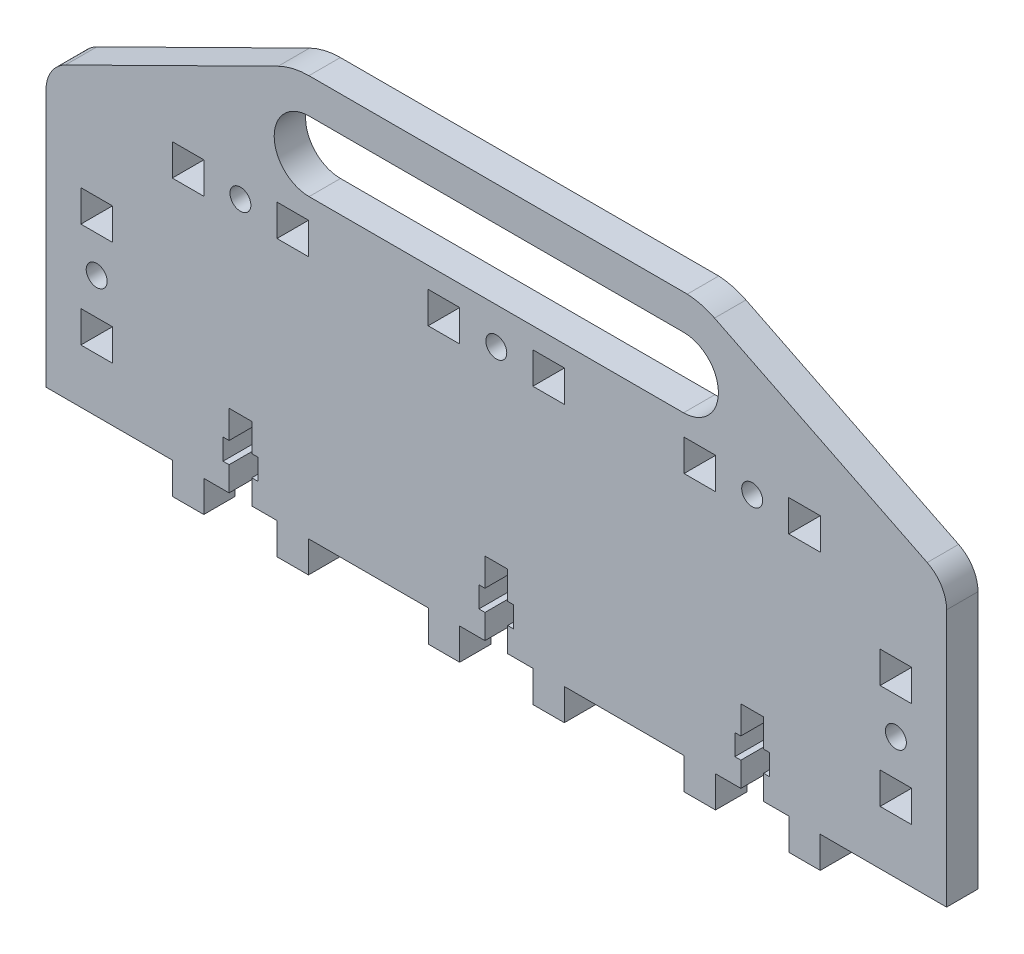
SolidWorks part; units mm, degrees
ref_plane "Front Plane" through (0, 0, 0) normal (0, 0, 1) x (1, 0, 0)
ref_plane "Top Plane" through (0, 0, 0) normal (0, 1, 0) x (1, 0, 0)
ref_plane "Right Plane" through (0, 0, 0) normal (1, 0, 0) x (0, 0, -1)
sketch "Sketch1" plane through (0, 0, 0) normal (0, 0, 1) x (1, 0, 0)
  line L0 (0, 35) -> (0, 0) construction
  line L1 (-110, 0) -> (110, 0)
  line L3 (-110, 70) -> (110, 70) construction
  line L5 (-110, 0) -> (110, 70) construction
  line L6 (-110, 70) -> (110, 0) construction
  line L7 (-53.6553, 95) -> (53.6553, 95) construction
  line L8 (-53.6553, 105) -> (53.6553, 105)
  line L9 (-53.6553, 85) -> (53.6553, 85)
  line L11 (-108.2938, 90.273) -> (-62.5269, 112.9247)
  line L12 (-53.6908, 115) -> (54.7434, 115)
  line L13 (62.5471, 112.9477) -> (117.7112, 85.6176)
  line L15 (0, 35) -> (110, 35) construction
  line L16 (110, 0) -> (129.05, 0)
  line L17 (129.05, 0) -> (129.05, 80)
  line L18 (129.05, 80) -> (117.7112, 85.6176)
  line L19 (-110, 0) -> (-129.05, 0)
  line L20 (-129.05, 0) -> (-129.05, 80)
  line L21 (-129.05, 80) -> (-108.2938, 90.273)
  line L22 (-110, 70) -> (-110, 0) construction
  line L23 (110, 70) -> (110, 0) construction
  arc A0 (-53.6553, 105) -> (-53.6553, 85) centre (-53.6553, 95) ccw
  arc A1 (53.6553, 85) -> (53.6553, 105) centre (53.6553, 95) ccw
  arc A2 (54.7434, 115) -> (62.5471, 112.9477) centre (53.6553, 95) cw
  arc A3 (-53.6908, 115) -> (-62.5269, 112.9247) centre (-53.6553, 95) ccw
  point P0 (0, 35)
  point P10 (0, 95)
  point P37 (-107.5694, 79.7001)
  line B0 (-19.5, 0) -> (-19.5, -9)
  line B1 (-19.5, -9) -> (-10.5, -9)
  line B2 (-10.5, -9) -> (-10.5, 0)
  line B3 (-10.5, 0) -> (-3.25, 0)
  line B4 (-3.25, 0) -> (-3.25, 7)
  line B5 (-3.25, 7) -> (-4.975, 7)
  line B6 (-4.975, 7) -> (-4.975, 13)
  line B7 (-4.975, 13) -> (-3.25, 13)
  line B8 (-3.25, 13) -> (-3.25, 21)
  line B9 (-3.25, 21) -> (3.25, 21)
  line B10 (0, 21) -> (0, 0) construction
  line B11 (3.25, 13) -> (3.25, 21)
  line B12 (4.975, 13) -> (3.25, 13)
  line B13 (4.975, 7) -> (4.975, 13)
  line B14 (3.25, 7) -> (4.975, 7)
  line B15 (3.25, 0) -> (3.25, 7)
  line B16 (10.5, 0) -> (3.25, 0)
  line B17 (10.5, -9) -> (10.5, 0)
  line B18 (19.5, -9) -> (10.5, -9)
  line B19 (19.5, 0) -> (19.5, -9)
  line B20 (-92.8333, 0) -> (-92.8333, -9)
  line B21 (-92.8333, -9) -> (-83.8333, -9)
  line B22 (-83.8333, -9) -> (-83.8333, 0)
  line B23 (-83.8333, 0) -> (-76.5833, 0)
  line B24 (-76.5833, 0) -> (-76.5833, 7)
  line B25 (-76.5833, 7) -> (-78.3083, 7)
  line B26 (-78.3083, 7) -> (-78.3083, 13)
  line B27 (-78.3083, 13) -> (-76.5833, 13)
  line B28 (-76.5833, 13) -> (-76.5833, 21)
  line B29 (-76.5833, 21) -> (-70.0833, 21)
  line B30 (-73.3333, 21) -> (-73.3333, 0) construction
  line B31 (-70.0833, 13) -> (-70.0833, 21)
  line B32 (-68.3583, 13) -> (-70.0833, 13)
  line B33 (-68.3583, 7) -> (-68.3583, 13)
  line B34 (-70.0833, 7) -> (-68.3583, 7)
  line B35 (-70.0833, 0) -> (-70.0833, 7)
  line B36 (-62.8333, 0) -> (-70.0833, 0)
  line B37 (-62.8333, -9) -> (-62.8333, 0)
  line B38 (-53.8333, -9) -> (-62.8333, -9)
  line B39 (-53.8333, 0) -> (-53.8333, -9)
  line B40 (53.8333, 0) -> (53.8333, -9)
  line B41 (53.8333, -9) -> (62.8333, -9)
  line B42 (62.8333, -9) -> (62.8333, 0)
  line B43 (62.8333, 0) -> (70.0833, 0)
  line B44 (70.0833, 0) -> (70.0833, 7)
  line B45 (70.0833, 7) -> (68.3583, 7)
  line B46 (68.3583, 7) -> (68.3583, 13)
  line B47 (68.3583, 13) -> (70.0833, 13)
  line B48 (70.0833, 13) -> (70.0833, 21)
  line B49 (70.0833, 21) -> (76.5833, 21)
  line B50 (73.3333, 21) -> (73.3333, 0) construction
  line B51 (76.5833, 13) -> (76.5833, 21)
  line B52 (78.3083, 13) -> (76.5833, 13)
  line B53 (78.3083, 7) -> (78.3083, 13)
  line B54 (76.5833, 7) -> (78.3083, 7)
  line B55 (76.5833, 0) -> (76.5833, 7)
  line B56 (83.8333, 0) -> (76.5833, 0)
  line B57 (83.8333, -9) -> (83.8333, 0)
  line B58 (92.8333, -9) -> (83.8333, -9)
  line B59 (92.8333, 0) -> (92.8333, -9)
  line B60 (-73.3333, 74.525) -> (-88.3333, 74.525) construction
  line B61 (-73.3333, 79.9951) -> (-73.3333, 69.5131) construction
  line B62 (-53.8083, 79.05) -> (-62.8583, 79.05)
  line B63 (-92.8583, 70) -> (-83.8083, 70)
  line B64 (-92.8583, 70) -> (-92.8583, 79.05)
  line B65 (-92.8583, 79.05) -> (-83.8083, 79.05)
  line B66 (-83.8083, 70) -> (-83.8083, 79.05)
  line B67 (-92.8583, 70) -> (-83.8083, 79.05) construction
  line B68 (-92.8583, 79.05) -> (-83.8083, 70) construction
  line B69 (-62.8583, 70) -> (-62.8583, 79.05)
  line B70 (-53.8083, 70) -> (-62.8583, 70)
  line B71 (-53.8083, 70) -> (-53.8083, 79.05)
  circle B72 centre (-73.3333, 74.525) radius 3
  line B73 (-114.525, 35) -> (-114.525, 20) construction
  line B74 (-119.9951, 35) -> (-109.5131, 35) construction
  line B75 (-119.05, 54.525) -> (-119.05, 45.475)
  line B76 (-110, 15.475) -> (-110, 24.525)
  line B77 (-110, 15.475) -> (-119.05, 15.475)
  line B78 (-119.05, 15.475) -> (-119.05, 24.525)
  line B79 (-110, 24.525) -> (-119.05, 24.525)
  line B80 (-110, 15.475) -> (-119.05, 24.525) construction
  line B81 (-119.05, 15.475) -> (-110, 24.525) construction
  line B82 (-110, 45.475) -> (-119.05, 45.475)
  line B83 (-110, 54.525) -> (-110, 45.475)
  line B84 (-110, 54.525) -> (-119.05, 54.525)
  circle B85 centre (-114.525, 35) radius 3
  line B86 (114.525, 35) -> (114.525, 20) construction
  line B87 (119.9951, 35) -> (109.5131, 35) construction
  line B88 (119.05, 54.525) -> (119.05, 45.475)
  line B89 (110, 15.475) -> (110, 24.525)
  line B90 (110, 15.475) -> (119.05, 15.475)
  line B91 (119.05, 15.475) -> (119.05, 24.525)
  line B92 (110, 24.525) -> (119.05, 24.525)
  line B93 (110, 15.475) -> (119.05, 24.525) construction
  line B94 (119.05, 15.475) -> (110, 24.525) construction
  line B95 (110, 45.475) -> (119.05, 45.475)
  line B96 (110, 54.525) -> (110, 45.475)
  line B97 (110, 54.525) -> (119.05, 54.525)
  circle B98 centre (114.525, 35) radius 3
  line B99 (0, 74.525) -> (-15, 74.525) construction
  line B100 (0, 79.9951) -> (0, 69.5131) construction
  line B101 (19.525, 79.05) -> (10.475, 79.05)
  line B102 (-19.525, 70) -> (-10.475, 70)
  line B103 (-19.525, 70) -> (-19.525, 79.05)
  line B104 (-19.525, 79.05) -> (-10.475, 79.05)
  line B105 (-10.475, 70) -> (-10.475, 79.05)
  line B106 (-19.525, 70) -> (-10.475, 79.05) construction
  line B107 (-19.525, 79.05) -> (-10.475, 70) construction
  line B108 (10.475, 70) -> (10.475, 79.05)
  line B109 (19.525, 70) -> (10.475, 70)
  line B110 (19.525, 70) -> (19.525, 79.05)
  circle B111 centre (0, 74.525) radius 3
  line B112 (73.3333, 74.525) -> (58.3333, 74.525) construction
  line B113 (73.3333, 79.9951) -> (73.3333, 69.5131) construction
  line B114 (92.8583, 79.05) -> (83.8083, 79.05)
  line B115 (53.8083, 70) -> (62.8583, 70)
  line B116 (53.8083, 70) -> (53.8083, 79.05)
  line B117 (53.8083, 79.05) -> (62.8583, 79.05)
  line B118 (62.8583, 70) -> (62.8583, 79.05)
  line B119 (53.8083, 70) -> (62.8583, 79.05) construction
  line B120 (53.8083, 79.05) -> (62.8583, 70) construction
  line B121 (83.8083, 70) -> (83.8083, 79.05)
  line B122 (92.8583, 70) -> (83.8083, 70)
  line B123 (92.8583, 70) -> (92.8583, 79.05)
  circle B124 centre (73.3333, 74.525) radius 3
  dimension "D1" = 70
  dimension "D2" = 220
  dimension "D3" = 45
  dimension "D4" = 25
  dimension "D5" = 20
  dimension "D7" = 10
  dimension "D6" = 80
  dimension "D8" = 36.6667
  dimension "D9" = 10
sketch_block_instance "Plot_9mm_M6_bois-1"
sketch_block "Plot_9mm_M6_bois" parameters "D1"=9, "D2"=9, "D3"=16, "D4"=30, "D5"=9.95, "D6"=6.5, "D7"=6, "D8"=8
sketch_block_instance "Plot_9mm_M6_bois-2"
sketch_block_instance "Plot_9mm_M6_bois-3"
sketch_block_instance "Insert_9mm_M6_bois-1"
sketch_block "Insert_9mm_M6_bois" parameters "D4"=6, "D1"=9.05, "D2"=9.05, "D3"=15
sketch_block_instance "Insert_9mm_M6_bois-2"
sketch_block_instance "Insert_9mm_M6_bois-5"
sketch_block_instance "Insert_9mm_M6_bois-6"
sketch_block_instance "Insert_9mm_M6_bois-7" parameters "D6"=10, "D8"=10, "D1"=58.0548, "D2"=145.7413, "D3"=128.3751, "D4"=108.4636, "D5"=108.4636, "D7"=4.1109, "D9"=55.9526, "D10"=74.7014
extrude "Boss-Extrude3" add sketch "Sketch1" along normal blind 9 contours L1 L16 L17 L18 L13 A2 L12 A3 L11 L21 L20 L19 | L1 | L1 | L1 | L1 | L1 | L1 | L1 | L1 | L1 | L1 region at (0.0046, 49.5728, 0) region at (-88.3333, -4.5, 0) region at (-58.3333, -4.5, 0) region at (-15, -4.5, 0) region at (15, -4.5, 0) region at (88.3333, -4.5, 0) region at (58.3333, -4.5, 0)
fillet "Fillet3" radius 10 2 edges at (-129.05, 80, 4.5) (129.05, 80, 4.5)
